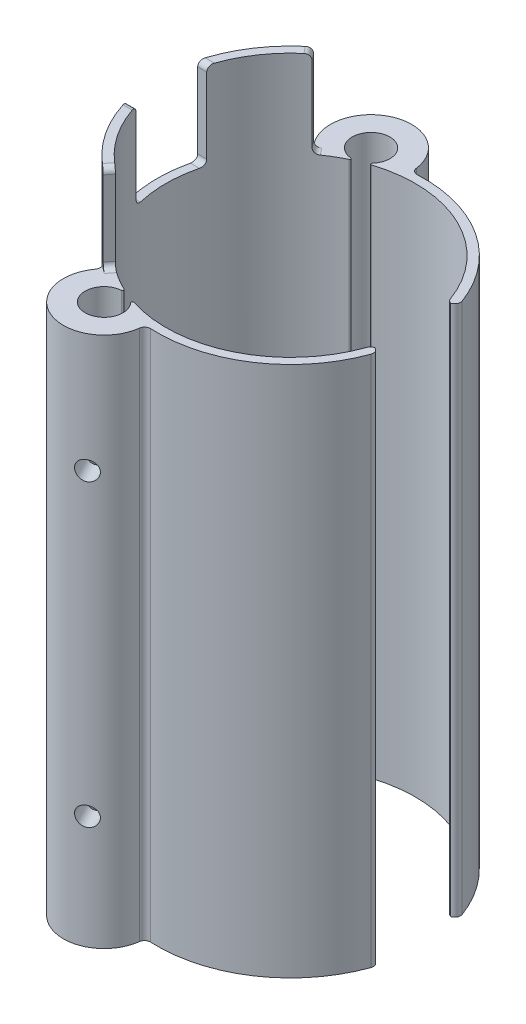
SolidWorks part; units mm, degrees
ref_plane "Plan de face" through (0, 0, 0) normal (0, 0, 1) x (1, 0, 0)
ref_plane "Plan de dessus" through (0, 0, 0) normal (0, 1, 0) x (1, 0, 0)
ref_plane "Plan de droite" through (0, 0, 0) normal (1, 0, 0) x (0, 0, -1)
ref_plane "Plan1" through (0, -85, 0) normal (0, 1, 0) x (1, 0, 0)
sketch "Esquisse2" plane through (0, -85, 0) normal (0, 1, 0) x (1, 0, 0)
  line L0 (-28, 23) -> (-28, -23) construction
  line L1 (-28, 0) -> (-14.7536, 0) construction
  line L2 (1.587, 6.65) -> (3.1589, 6.65)
  line L3 (50, 6.65) -> (-80, 6.65) construction
  line L4 (1.6509, -6.45) -> (3.2183, -6.45)
  line L6 (50, -6.45) -> (-80, -6.45) construction
  arc A1 (-21.0007, 22.9) -> (-33.0211, 18.1226) centre (-28, 23) ccw
  arc A2 (1.6509, -6.45) -> (-25.3911, -20.4836) centre (-18.8587, 0) cw
  arc A3 (-33.0211, 18.1226) -> (-33.0211, -18.1226) centre (-18.8587, 0) ccw
  arc A4 (-25.5996, 20.809) -> (-28.2415, 19.759) centre (-28, 23) ccw
  arc A5 (-33.0211, -18.1226) -> (-21.0007, -22.9) centre (-28, -23) ccw
  arc A6 (-28.2415, -19.759) -> (-25.5996, -20.809) centre (-28, -23) ccw
  arc A7 (-21.0007, -22.9) -> (3.2183, -6.45) centre (-18.8587, 0) ccw
  arc A8 (-25.5996, -20.809) -> (-25.3911, -20.4836) centre (-25.4519, -20.6742) cw
  arc A10 (1.587, 6.65) -> (-25.3911, 20.4836) centre (-18.8587, 0) ccw
  arc A11 (3.1589, 6.65) -> (-21.0007, 22.9) centre (-18.8587, 0) ccw
  arc A12 (-25.3911, 20.4836) -> (-25.5996, 20.809) centre (-25.4519, 20.6742) cw
  arc A13 (-28.1697, 19.3793) -> (-28.1697, -19.3793) centre (-18.8587, 0) ccw
  arc A14 (-28.1697, -19.3793) -> (-28.2415, -19.759) centre (-28.2563, -19.5595) cw
  arc A15 (-28.2415, 19.759) -> (-28.1697, 19.3793) centre (-28.2563, 19.5595) cw
  dimension "D1" = 46
  dimension "D2" = 14
  dimension "D3" = 6.5
  dimension "D4" = 6.5
  dimension "D5" = 14
  dimension "D6" = 43
  dimension "D7" = 0.2
  dimension "D8" = 0.2
  dimension "D9" = 0.2
  dimension "D10" = 0.2
extrude "Boss.-Extru.1" add sketch "Esquisse2" against normal up to surface (91.541 mm away)
sketch "Esquisse3" plane through (0, -85, 0) normal (0, 1, 0) x (1, 0, 0)
  line L0 (-33.0211, 18.1226) -> (-32.0974, 16.9407)
  line L1 (-33.0211, -18.1226) -> (-32.0974, -16.9407)
  line L2 (-32.2328, -16.8349) -> (-31.9621, -17.0464) construction
  line L3 (-38.6996, 11.7813) -> (-25.4952, 22.1001) construction
  line L4 (-41.0213, 6.15) -> (-39.4604, 6.15)
  line L6 (-41.0758, -5.95) -> (-39.519, -5.95)
  line L8 (-82.5, 5.65) -> (54, 5.65) construction
  line L9 (54, -5.45) -> (-82.5, -5.45) construction
  arc A1 (-33.0211, 18.1226) -> (-33.0211, -18.1226) centre (-18.8587, 0) ccw construction
  arc A2 (-33.0211, 18.1226) -> (-41.0213, 6.15) centre (-18.8587, 0) ccw
  arc A3 (-32.0974, 16.9407) -> (-39.4604, 6.15) centre (-18.8587, 0) ccw
  arc A4 (-41.0758, -5.95) -> (-33.0211, -18.1226) centre (-18.8587, 0) ccw
  arc A5 (-28.1697, 19.3793) -> (-28.1697, -19.3793) centre (-18.8587, 0) ccw construction
  arc A13 (-39.519, -5.95) -> (-32.0974, -16.9407) centre (-18.8587, 0) ccw
  dimension "D1" = 0.5
  dimension "D2" = 0.5
extrude "Boss.-Extru.2" add sketch "Esquisse3" along normal blind 15
sketch "Esquisse4" plane through (0, -176.541, 0) normal (0, -1, 0) x (1, 0, 0)
  line L0 (-28, 23) -> (-0.6535, 75)
  line L1 (-28, -23) -> (-0.6535, -75)
ref_plane "Plan2" through (-31.409, 0, 16.5178) normal (-0.8851, 0, 0.4655) x (0.4655, 0, 0.8851)
ref_plane "Plan3" through (6.6671, 0, 12.6777) normal (0.4655, 0, 0.8851) x (0.8851, 0, -0.4655)
hole_wizard "Trou pour taraudage pour trou taraudé M41" positions "Esquisse5" profile "Esquisse6" hole size "M4" standard "ISO" end condition up to next
sketch "Esquisse5" plane through (6.6671, 0, 12.6777) normal (0.4655, 0, 0.8851) x (0.8851, 0, -0.4655)
  line L0 (-35.4875, 26.624) -> (-35.4875, -26.624) construction
  point P0 (-35.4875, -157.0245)
  point P4 (-35.4875, -105.4534)
sketch "Esquisse6" plane through (-24.7418, -157.0245, 29.1955) normal (0, 1, 0) x (0.8851, 0, -0.4655)
  line L0 (0, 0) -> (0, 12.6636)
  line L1 (0, 12.6636) -> (1.65, 12.6636)
  line L2 (1.65, 12.6636) -> (1.65, 0)
  line L5 (1.65, 0) -> (0, 0)
  line L11 (0, -6.35) -> (0, 107.95) construction
  dimension "Diamètre du perçage jusqu'au prochain" = 3.3
  dimension "Profondeur du perçage jusqu'au prochain" = 12.6636
mirror "Symétrie1" about plane through (0, 0, 0) normal (0, 0, 1) of "Trou pour taraudage pour trou taraudé M41"
fillet "Congé3" radius 1 14 edges at (-33.0211, -130.7705, -18.1226) (-33.0211, -130.7705, 18.1226) (-21.0007, -130.7705, 22.9) (-32.5592, -70, 17.5317) (-32.5592, -70, -17.5317) (-40.2974, -85, 5.95) (-40.2974, -70, 5.95) (-40.2408, -70, -6.15) (-40.2408, -85, -6.15) (3.2183, -130.7705, 6.45) (1.6509, -130.7705, 6.45) (3.1589, -130.7705, -6.65) (1.587, -130.7705, -6.65) (-21.0007, -130.7705, -22.9)
fillet "Congé5" radius 1 2 edges at (-32.5592, -85, -17.5317) (-32.5592, -85, 17.5317)
